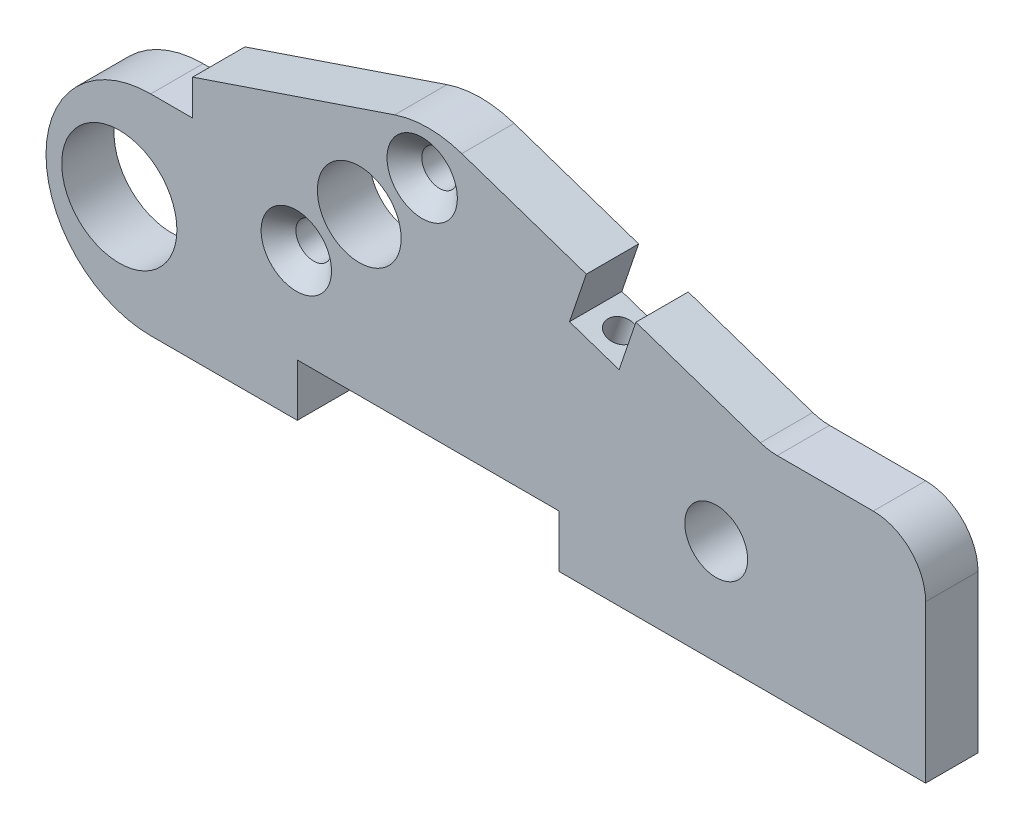
SolidWorks part; units mm, degrees
ref_plane "Front Plane" through (0, 0, 0) normal (0, 0, 1) x (1, 0, 0)
ref_plane "Top Plane" through (0, 0, 0) normal (0, 1, 0) x (1, 0, 0)
ref_plane "Right Plane" through (0, 0, 0) normal (1, 0, 0) x (0, 0, -1)
sketch "Sketch1" plane through (0, 0, 0) normal (0, 0, 1) x (1, 0, 0)
  line L0 (37.697, 7.4194) -> (5.197, 18.4194)
  line L1 (5.197, -12.5806) -> (5.197, 23.3572) construction
  line L2 (-31.303, -12.5806) -> (52.697, -12.5806)
  line L5 (-27.303, 7.4194) -> (-31.303, 7.4194)
  line L6 (-27.303, 7.4194) -> (-17.303, 7.4194)
  line L7 (-17.303, 7.4194) -> (-17.303, 10.8091)
  line L8 (-17.303, 10.8091) -> (5.197, 18.4194)
  line L9 (-31.303, 7.4194) -> (-31.303, -12.5806)
  line L11 (52.697, -12.5806) -> (52.697, 7.4194)
  line L12 (52.697, 7.4194) -> (37.697, 7.4194)
  dimension "D3" = 10
  dimension "D1" = 65
  dimension "D4" = 4
  dimension "D7" = 31
  dimension "D8" = 15
extrude "Boss-Extrude1" add sketch "Sketch1" along normal blind 5
sketch "Sketch2" plane through (0, 0, 5) normal (0, 0, 1) x (1, 0, 0)
  line L0 (-24.303, -2.5806) -> (-4.303, -2.5806) construction
  line L2 (-4.303, -2.5806) -> (-10.3134, -8.591) construction
  line L3 (-27.303, -2.5806) -> (-24.303, -2.5806) construction
  line L4 (-4.303, -2.5806) -> (-12.803, -2.5806) construction
  line L5 (-4.303, -2.5806) -> (1.7074, 3.4298) construction
  line L6 (-4.303, -2.5806) -> (4.197, -2.5806) construction
  line L7 (37.697, -2.5806) -> (32.697, -2.5806) construction
  circle A0 centre (-24.303, -2.5806) radius 25
  dimension "D6" = 8.5
  dimension "D8" = 50
  dimension "D1" = 3
  dimension "D2" = 20
  dimension "D3" = 8.5
  dimension "D4" = 8.5
  dimension "D5" = 8.5
  dimension "D7" = 5
hole_wizard "Ø11.0 (11) Diameter Hole1" positions "3DSketch2" profile "Sketch4" hole size "Ø11.0" standard "ISO"
sketch3d "3DSketch2"
  point P0 (-24.303, -2.5806, 5)
sketch "Sketch4" plane through (-24.303, -2.5806, 5) normal (1, 0, 0) x (0, -1, 0)
  line L0 (0, 0) -> (0, 28.3047)
  line L1 (0, 28.3047) -> (5.5, 25)
  line L2 (5.5, 25) -> (5.5, 0)
  line L5 (5.5, 0) -> (0, 0)
  line L10 (0, 28.3047) -> (-5.5, 25) construction
  line L11 (0, -6.35) -> (0, 107.95) construction
  dimension "Hole Dia." = 11
  dimension "Hole Depth" = 25
  dimension "Drill Angle" = 118
hole_wizard "Ø6.0mm Dowel Hole1" positions "3DSketch6" profile "Sketch9" hole size "Ø6.0" standard "ISO"
sketch3d "3DSketch6"
  point P0 (32.697, -2.5806, 5)
sketch "Sketch9" plane through (32.697, -2.5806, 5) normal (1, 0, 0) x (0, -1, 0)
  line L0 (0, 0) -> (0, 26.8026)
  line L1 (0, 26.8026) -> (3, 25)
  line L2 (3, 25) -> (3, 0)
  line L5 (3, 0) -> (0, 0)
  line L10 (0, 26.8026) -> (-3, 25) construction
  line L11 (0, -6.35) -> (0, 107.95) construction
  dimension "Hole Dia." = 6
  dimension "Hole Depth" = 25
  dimension "Drill Angle" = 118
sketch "Sketch22" plane through (0, 0, 0) normal (0, 0, -1) x (-1, 0, 0)
  line L0 (-37.697, -2.5806) -> (-17.697, -2.5806) construction
  line L1 (-17.697, -2.5806) -> (-17.697, -12.5806) construction
  line L3 (-17.697, -12.5806) -> (-17.697, -7.5806)
  line L4 (-17.697, -7.5806) -> (7.303, -7.5806)
  line L5 (7.303, -7.5806) -> (7.303, -12.5806)
  line L6 (7.303, -12.5806) -> (-17.697, -12.5806)
  dimension "D1" = 20
  dimension "D2" = 5
  dimension "D3" = 25
extrude "Cut-Extrude1" cut sketch "Sketch22" against normal blind 10
sketch "Sketch34" plane through (0, 0, 5) normal (0, 0, 1) x (1, 0, 0)
  line L0 (-1.3901, -12.5806) -> (-1.3901, 7.4194) construction
  line L2 (-24.303, -2.5806) -> (-1.3901, 7.4194) construction
  circle A0 centre (-24.303, -2.5806) radius 25 construction
  circle A1 centre (-1.3901, 7.4194) radius 12.5
  dimension "D1" = 25
hole_wizard "Ø8.0mm Dowel Hole2" positions "Sketch36" profile "Sketch35" hole size "Ø8.0" standard "ISO"
sketch "Sketch36" plane through (0, 0, 5) normal (0, 0, 1) x (1, 0, 0)
  point P0 (-1.3901, 7.4194)
sketch "Sketch35" plane through (-1.3901, 7.4194, 5) normal (1, 0, 0) x (0, -1, 0)
  line L0 (0, 0) -> (0, 22.4034)
  line L1 (0, 22.4034) -> (4, 20)
  line L2 (4, 20) -> (4, 0)
  line L5 (4, 0) -> (0, 0)
  line L10 (0, 22.4034) -> (-4, 20) construction
  line L11 (0, -6.35) -> (0, 107.95) construction
  dimension "Hole Dia." = 8
  dimension "Hole Depth" = 20
  dimension "Drill Angle" = 118
sketch "Sketch37" plane through (0, 0, 5) normal (0, 0, 1) x (1, 0, 0)
  line L0 (-1.3901, 7.4194) -> (-7.4005, 1.409) construction
  line L1 (-1.3901, 7.4194) -> (4.6203, 13.4298) construction
  dimension "D1" = 8.5
  dimension "D2" = 8.5
hole_wizard "CSK for M3 Hex Socket Countersunk Cap Screw1" positions "Sketch41" profile "Sketch40" countersink size "M3" standard "ISO" end condition through all
sketch "Sketch41" plane through (0, 0, 5) normal (0, 0, 1) x (1, 0, 0)
  point P0 (-7.4005, 1.409)
  point P3 (4.6203, 13.4298)
sketch "Sketch40" plane through (-7.4005, 1.409, 5) normal (1, 0, 0) x (0, -1, 0)
  line L0 (0, 0) -> (0, 5)
  line L1 (0, 5) -> (1.7, 5)
  line L2 (1.7, 5) -> (1.7, 1.66)
  line L3 (1.7, 1.66) -> (3.36, 0)
  line L5 (3.36, 0) -> (0, 0)
  line L6 (-1.7, 1.66) -> (-3.36, 0) construction
  line L11 (0, -6.35) -> (0, 107.95) construction
  dimension "Thru Hole Dia." = 3.4
  dimension "Thru Hole Depth" = 5
  dimension "Near C'Sink Dia." = 6.72
  dimension "Near C'Sink Angle" = 90
sketch "Sketch43" plane through (0, -7.5806, 0) normal (0, -1, 0) x (1, 0, 0)
  line L0 (5.197, 2.5) -> (-7.303, 2.5) construction
  line L3 (5.197, 2.5) -> (5.197, 0) construction
  line L4 (-7.303, 0) -> (17.697, 0) construction
  line L5 (-7.303, 5) -> (-7.303, 0) construction
  line L6 (-1.053, 2.5) -> (-1.053, 5) construction
  line L7 (17.697, 5) -> (-7.303, 5) construction
  line L8 (5.197, 2.5) -> (17.697, 2.5) construction
  line L9 (17.697, 5) -> (17.697, 0) construction
  line L10 (11.447, 2.5) -> (11.447, 5) construction
hole_wizard "M3 Tapped Hole1" positions "Sketch45" profile "Sketch44" tap size "M3" standard "ISO"
sketch "Sketch45" plane through (0, -7.5806, 0) normal (0, -1, 0) x (-1, 0, 0)
  point P0 (1.053, -2.5)
  point P3 (-11.447, -2.5)
sketch "Sketch44" plane through (-1.053, -7.5806, 2.5) normal (1, 0, 0) x (0, 0, -1)
  line L0 (0, 0) -> (0, 8.2511)
  line L1 (0, 8.2511) -> (1.25, 7.5)
  line L2 (1.25, 7.5) -> (1.25, 0)
  line L5 (1.25, 0) -> (0, 0)
  line L10 (0, 8.2511) -> (-1.25, 7.5) construction
  line L11 (0, -6.35) -> (0, 107.95) construction
  dimension "Tap Drill Dia." = 2.5
  dimension "Tap Drill Depth" = 7.5
  dimension "Drill Angle" = 118
cosmetic thread "Hole Thread1" parameters "D1"=6, "D2"=3
cosmetic thread "Hole Thread2" parameters "D1"=6, "D2"=3
sketch "Sketch46" plane through (0, 0, 5) normal (0, 0, 1) x (1, 0, 0)
  circle A0 centre (-24.303, -2.5806) radius 7.5
  dimension "D1" = 15
fillet "Fillet2" radius 10 1 edges at (5.197, 18.4194, 2.5)
fillet "Fillet3" radius 10 2 edges at (-31.303, -12.5806, 2.5) (-31.303, 7.4194, 2.5)
fillet "Fillet4" radius 5 2 edges at (52.697, 7.4194, 2.5) (37.697, 7.4194, 2.5)
sketch "Sketch47" plane through (0, 0, 0) normal (0, 0, -1) x (-1, 0, 0)
  line L0 (-36.9172, 7.6833) -> (-8.4019, 17.3346) construction
  line L1 (-8.4019, 17.3346) -> (-6.7989, 12.5986) construction
  line L2 (-6.7989, 12.5986) -> (-35.3143, 2.9472) construction
  line L3 (-35.3143, 2.9472) -> (-36.9172, 7.6833) construction
  line L4 (-21.0566, 7.7729) -> (-22.6596, 12.509) construction
  line L6 (-18.6885, 8.5744) -> (-20.2915, 13.3105)
  line L7 (-20.2915, 13.3105) -> (-25.0276, 11.7075)
  line L8 (-25.0276, 11.7075) -> (-23.4246, 6.9714)
  line L9 (-23.4246, 6.9714) -> (-18.6885, 8.5744)
  dimension "D1" = 5
  dimension "D2" = 2.5
  dimension "D3" = 2.5
  dimension "D4" = 5
extrude "Cut-Extrude2" cut sketch "Sketch47" against normal blind 10
hole_wizard "M3 Tapped Hole2" positions "Sketch51" profile "Sketch50" tap size "M3" standard "ISO"
sketch "Sketch51" plane through (4.5247, 13.3683, 0) normal (0.3206, 0.9472, 0) x (0.9472, -0.3206, 0)
  line L0 (19.9532, -2.5) -> (17.4532, -2.5023) construction
  line L1 (19.9532, -5) -> (19.9532, 0) construction
  line L2 (17.4532, -2.5023) -> (17.4532, 0) construction
  line L3 (19.9532, 0) -> (14.9532, 0) construction
  point P0 (17.4532, -2.5023)
sketch "Sketch50" plane through (21.0566, 7.7729, 2.5023) normal (0, 0, 1) x (-0.9472, 0.3206, 0)
  line L0 (0, 0) -> (0, 8.7511)
  line L1 (0, 8.7511) -> (1.25, 8)
  line L2 (1.25, 8) -> (1.25, 0)
  line L5 (1.25, 0) -> (0, 0)
  line L10 (0, 8.7511) -> (-1.25, 8) construction
  line L11 (0, -6.35) -> (0, 107.95) construction
  dimension "Tap Drill Dia." = 2.5
  dimension "Tap Drill Depth" = 8
  dimension "Drill Angle" = 118
cosmetic thread "Hole Thread3" parameters "D1"=6, "D2"=3
